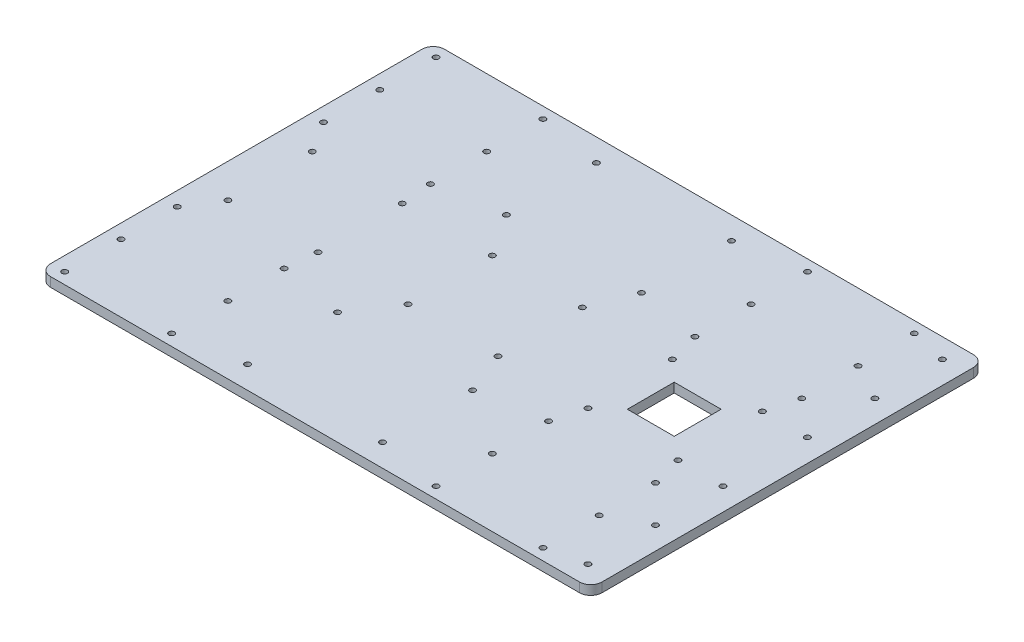
SolidWorks part; units mm, degrees
ref_plane "Front Plane" through (0, 0, 0) normal (0, 0, 1) x (1, 0, 0)
ref_plane "Top Plane" through (0, 0, 0) normal (0, 1, 0) x (1, 0, 0)
ref_plane "Right Plane" through (0, 0, 0) normal (1, 0, 0) x (0, 0, -1)
sketch "Sketch1" plane through (0, 0, 0) normal (0, 1, 0) x (1, 0, 0)
  line L0 (-127.5, 105) -> (-127.5, -105) construction
  line L1 (-129, -105) -> (129, -105)
  line L2 (-135, -99) -> (-135, 99)
  line L3 (-129, 105) -> (129, 105)
  line L4 (135, -99) -> (135, 99) construction
  line L5 (-135, -105) -> (135, 105) construction
  line L6 (-135, 105) -> (135, -105) construction
  line L8 (0, 105) -> (0, -105) construction
  line L9 (-135, 0) -> (135, 0) construction
  line L13 (129, 105) -> (153, 105)
  line L14 (159, 99) -> (159, -99)
  line L15 (153, -105) -> (129, -105)
  line L16 (147, 105) -> (147, -105) construction
  line L17 (159, -22.5) -> (-135, -22.5) construction
  line L19 (86, -12.5) -> (111, -12.5)
  line L20 (86, -12.5) -> (86, 12.5)
  line L21 (86, 12.5) -> (111, 12.5)
  line L22 (111, -12.5) -> (111, 12.5)
  line L23 (86, -12.5) -> (111, 12.5) construction
  line L24 (86, 12.5) -> (111, -12.5) construction
  line L25 (-36, -93) -> (36, -93) construction
  line L26 (-36, -93) -> (-36, -45) construction
  line L27 (-36, -45) -> (36, -45) construction
  line L28 (36, -93) -> (36, -45) construction
  line L29 (-36, -93) -> (36, -45) construction
  line L30 (-36, -45) -> (36, -93) construction
  circle A0 centre (-127.5, 99) radius 1.5
  circle A1 centre (-127.5, 69) radius 1.5
  circle A2 centre (-127.5, 39) radius 1.5
  circle A3 centre (-70.5, 99) radius 1.5
  circle A4 centre (-70.5, 69) radius 1.5
  circle A5 centre (-70.5, 39) radius 1.5
  circle A6 centre (70.5, 39) radius 1.5
  circle A7 centre (70.5, 69) radius 1.5
  circle A8 centre (70.5, 99) radius 1.5
  circle A9 centre (127.5, 39) radius 1.5
  circle A10 centre (127.5, 69) radius 1.5
  circle A11 centre (127.5, 99) radius 1.5
  circle A12 centre (127.5, -99) radius 1.5
  circle A13 centre (127.5, -69) radius 1.5
  circle A14 centre (127.5, -39) radius 1.5
  circle A15 centre (70.5, -99) radius 1.5
  circle A16 centre (70.5, -69) radius 1.5
  circle A17 centre (70.5, -39) radius 1.5
  circle A18 centre (-70.5, -39) radius 1.5
  circle A19 centre (-70.5, -69) radius 1.5
  circle A20 centre (-70.5, -99) radius 1.5
  circle A21 centre (-127.5, -39) radius 1.5
  circle A22 centre (-127.5, -69) radius 1.5
  circle A23 centre (-127.5, -99) radius 1.5
  arc A37 (129, 105) -> (135, 99) centre (129, 99) cw construction
  arc A38 (135, -99) -> (129, -105) centre (129, -99) cw construction
  arc A39 (-129, -105) -> (-135, -99) centre (-129, -99) cw
  arc A40 (-135, 99) -> (-129, 105) centre (-129, 99) cw
  arc A43 (153, -105) -> (159, -99) centre (153, -99) ccw
  arc A44 (159, 99) -> (153, 105) centre (153, 99) ccw
  circle A45 centre (147, -94.5) radius 1.5
  circle A46 centre (147, -58.5) radius 1.5
  circle A47 centre (147, -22.5) radius 1.5
  circle A51 centre (123, -22.5) radius 1.5
  circle A52 centre (75, -22.5) radius 1.5
  circle A53 centre (27, -22.5) radius 1.5
  circle A54 centre (-21, -22.5) radius 1.5
  circle A55 centre (-69, -22.5) radius 1.5
  circle A56 centre (-117, -22.5) radius 1.5
  circle A57 centre (-36, -93) radius 1.5
  circle A58 centre (36, -93) radius 1.5
  circle A59 centre (36, -45) radius 1.5
  circle A60 centre (-36, -45) radius 1.5
  circle A61 centre (123, 22.5) radius 1.5
  circle A62 centre (75, 22.5) radius 1.5
  circle A63 centre (27, 22.5) radius 1.5
  circle A64 centre (-21, 22.5) radius 1.5
  circle A65 centre (-69, 22.5) radius 1.5
  circle A66 centre (-117, 22.5) radius 1.5
  circle A67 centre (36, 93) radius 1.5
  circle A68 centre (36, 45) radius 1.5
  circle A69 centre (-36, 45) radius 1.5
  circle A70 centre (-36, 93) radius 1.5
  circle A71 centre (147, 94.5) radius 1.5
  circle A72 centre (147, 58.5) radius 1.5
  circle A73 centre (147, 22.5) radius 1.5
  point P0 (0, 0)
  point P59 (0, 0)
  point P72 (98.5, 0)
  point P88 (0, 0)
  point P93 (0, -69)
  point P98 (0, 0)
  dimension "D5" = 3
  dimension "D9" = 22.5
  dimension "D10" = 24
  dimension "D11" = 6
  dimension "D14" = 57
  dimension "D15" = 3
  dimension "D17" = 36
  dimension "D18" = 25
  dimension "D19" = 6
  dimension "D12" = 3
  dimension "D21" = 3
  dimension "D23" = 24
  dimension "D24" = 48
  dimension "D25" = 3
  dimension "D1" = 270
  dimension "D2" = 210
  dimension "D3" = 7.5
  dimension "D4" = 3
  dimension "D6" = 6
  dimension "D8" = 12
  dimension "D13" = 30
  dimension "D20" = 48
  dimension "D26" = 12
  dimension "D27" = 48
  dimension "D28" = 72
  dimension "D7" = 2
  dimension "D22" = 6
extrude "Boss-Extrude1" add sketch "Sketch1" along normal blind 5
